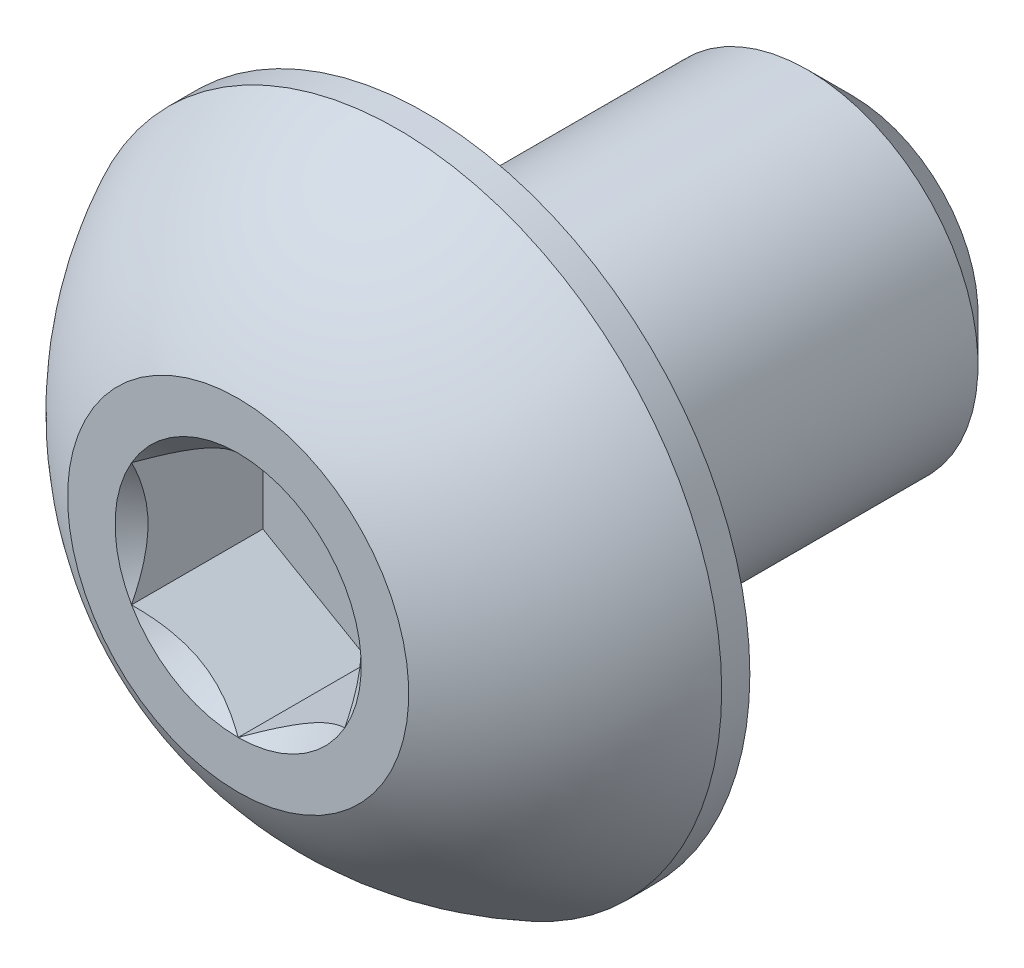
SolidWorks part; units mm, degrees
ref_plane "Front" through (0, 0, 0) normal (0, 0, 1) x (1, 0, 0)
ref_plane "Top" through (0, 0, 0) normal (0, 1, 0) x (1, 0, 0)
ref_plane "Right" through (0, 0, 0) normal (1, 0, 0) x (0, 0, -1)
sketch "Sketch1" plane through (0, 0, 0) normal (1, 0, 0) x (0, 0, -1)
  line L2 (2.2, 2) -> (7.2, 2)
  line L3 (7.2, 2) -> (7.2, 0)
  line L4 (7.2, 0) -> (2.2, 0)
  line L6 (1.87, 3.8) -> (2.2, 3.8) construction
  line L7 (7.2, 2) -> (7.2, -2) construction
  line L8 (0, 0) -> (2.2, 0) construction
  line L9 (2.2, 3.8) -> (2.2, -3.8) construction
  line L11 (2.2, 2) -> (2.2, 0)
  line L13 (0, 1.25) -> (0, -1.25) construction
  line L14 (0, 1.25) -> (0, 2) construction
  arc A3 (0, 2) -> (1.87, 3.8) centre (3.7264, 0) cw construction
  dimension "D1" = 0.33
revolve "Revolve1" add sketch "Sketch1" angle 360 mid plane about L4
sketch "Sketch3" plane through (0, 0, -7.2) normal (0, 0, -1) x (-1, 0, 0)
  circle A0 centre (0, 0) radius 2
curve "Helix/Spiral1" pitch 0.7 height 5.7 turns 8.1429
chamfer "Chamfer1" distance 0.525 angle 45 1 edges at (0, 2, -7.2)
sketch "Sketch7" plane through (0, 0, 0) normal (1, 0, 0) x (0, 0, -1)
  line L6 (1.87, 3.8) -> (2.2, 3.8) construction
  line L8 (0, 0) -> (2.2, 0) construction
  line L11 (2.2, 3.8) -> (2.2, -3.8) construction
  line L12 (1.87, 3.8) -> (2.2, 3.8)
  line L13 (0, 0) -> (2.2, 0)
  line L14 (0, 1.25) -> (0, -1.25) construction
  line L15 (2.2, 3.8) -> (2.2, 0)
  line L16 (0, 2) -> (0, 0)
  arc A2 (1.87, 3.8) -> (0, 2) centre (3.7264, 0) ccw construction
  arc A3 (1.87, 3.8) -> (0, 2) centre (3.7264, 0) ccw
revolve "Revolve2" add sketch "Sketch7" angle 360 mid plane about L13
sketch "Sketch5" plane through (0, 0, 0) normal (0, 0, 1) x (1, 0, 0)
  line L1 (1.25, -0.7217) -> (1.25, 0.7217)
  line L2 (1.25, 0.7217) -> (0, 1.4434)
  line L3 (0, 1.4434) -> (-1.25, 0.7217)
  line L4 (-1.25, 0.7217) -> (-1.25, -0.7217)
  line L5 (-1.25, -0.7217) -> (0, -1.4434)
  line L6 (0, -1.4434) -> (1.25, -0.7217)
  circle A0 centre (0, 0) radius 1.25 construction
extrude "Cut-Extrude2" cut sketch "Sketch5" against normal blind 1.54
sketch "Sketch6" plane through (0, 0, 0) normal (0, 0, 1) x (1, 0, 0)
  circle A0 centre (0, 0) radius 1.4434
extrude "Cut-Extrude3" cut sketch "Sketch6" against normal blind 1.54 draft 45
sketch "Sketch2" plane through (0, 0, 0) normal (1, 0, 0) x (0, 0, -1)
  line L0 (6.675, 2) -> (7.2875, 2)
  line L1 (7.2875, 2) -> (7.025, 1.5453)
  line L2 (7.025, 1.5453) -> (6.9375, 1.5453)
  line L3 (6.9375, 1.5453) -> (6.675, 2)
  line L4 (6.8062, 1.7727) -> (7.1562, 1.7727) construction
  dimension "D1" = 60
  dimension "D2" = 0.0875
  dimension "D3" = 0.35
sweep "Cut-Sweep1" [suppressed] cut profiles "Sketch2" path "Helix/Spiral1"
sketch "Sketch10" plane through (0, 0, 0) normal (1, 0, 0) x (0, 0, -1)
  line L0 (7.2, 2) -> (7.2, -2) construction
  point P0 (6.15, -2)
  dimension "D1" = 1.05
ref_axis "Center Axis 1" through (0, 0, -8.1113) along (0, 0, 1)
ref_plane "Contact Plane 1" through (0, 0, -2.2) normal (0, 0, -1) x (-1, 0, 0)
ref_plane "Contact Plane 2" through (0, 0, 0) normal (0, 0, 1) x (1, 0, 0)
equation "\"D3@Helix/Spiral1\" = \"Lg@Sketch1\" + \"D4@Helix/Spiral1\""
equation "\"D2@Sketch2\" = \"D4@Helix/Spiral1\" * .125"
equation "\"D3@Sketch2\" = \"D4@Helix/Spiral1\" * .5"
equation "\"D1@Chamfer1\" = \"D4@Helix/Spiral1\" * .75"
equation "\"D1@Cut-Extrude2\" = \"Head Ht@Sketch1\" * .7"
equation "\"D1@Sketch1\" = \"Head Ht@Sketch1\" * .15"
equation "\"D1@Sketch10\" = \"D4@Helix/Spiral1\" * 1.5"
equation "\"D1@Cut-Extrude3\" = \"D1@Cut-Extrude2\""
